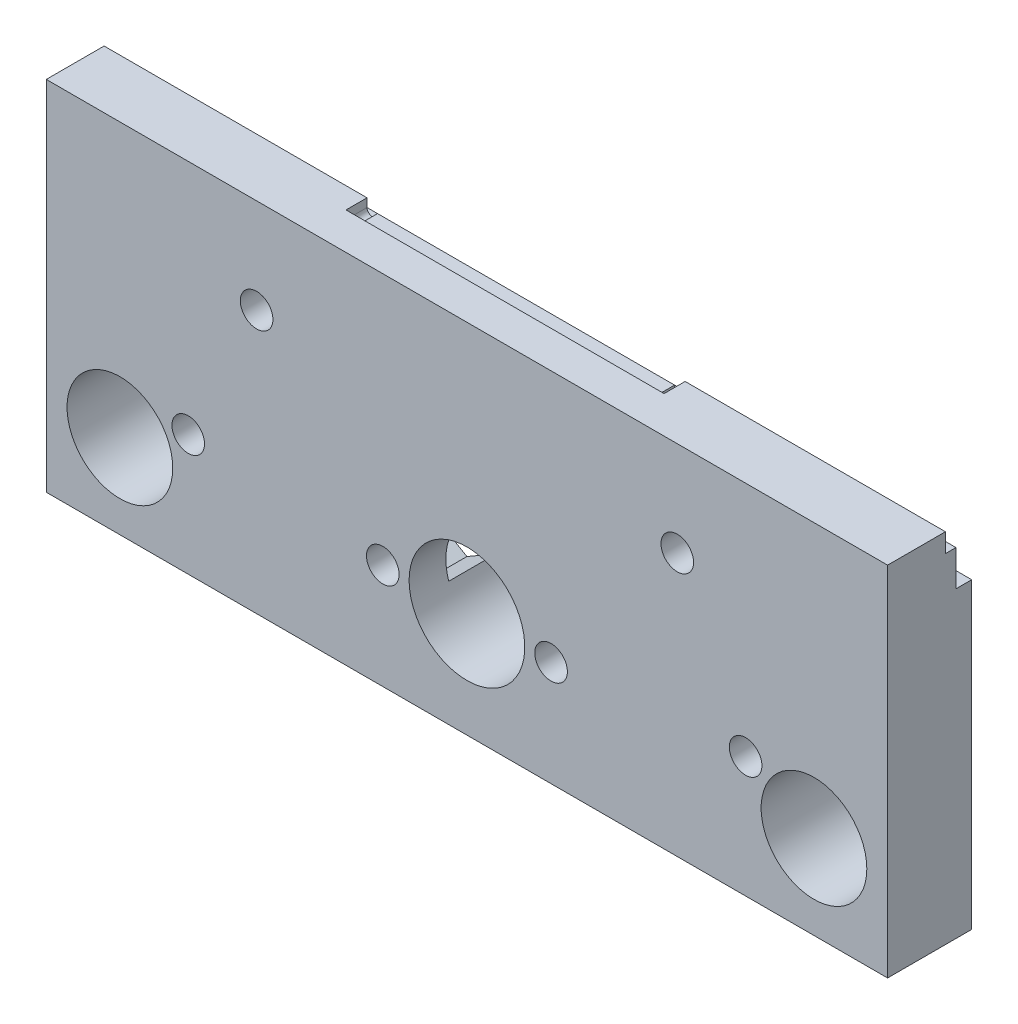
SolidWorks part; units mm, degrees
ref_plane "前视基准面" through (0, 0, 0) normal (0, 0, 1) x (1, 0, 0)
ref_plane "上视基准面" through (0, 0, 0) normal (0, 1, 0) x (1, 0, 0)
ref_plane "右视基准面" through (0, 0, 0) normal (1, 0, 0) x (0, 0, -1)
sketch "前视图草图" plane through (0, 0, 0) normal (0, 0, 1) x (1, 0, 0)
  line L0 (0, 0) -> (44.4821, 0) construction
  line L1 (0, 0) -> (0, 28.3185) construction
sketch "草图2" plane through (0, 0, 0) normal (0, 0, 1) x (1, 0, 0)
  line L0 (0, 0) -> (80, 0)
  line L1 (-200000, 0) -> (200044.4821, 0) construction
  line L2 (80, 0) -> (80, 34)
  line L3 (80, 34) -> (0, 34)
  line L4 (0, -200000) -> (0, 200028.3185) construction
  line L5 (0, 34) -> (0, 0)
  circle A0 centre (7, 8) radius 5.025
  circle A1 centre (40, 10) radius 4.05
  circle A2 centre (73, 8) radius 5.025
  dimension "D3" = 8
  dimension "D5" = 10
  dimension "D9" = 10.05
  dimension "D10" = 10.05
  dimension "D11" = 8.1
  dimension "D1" = 34
  dimension "D2" = 80
  dimension "D4" = 7
  dimension "D6" = 7
  dimension "D7" = 8
  dimension "D8" = 40
extrude "凸台-拉伸1" add sketch "草图2" along normal blind 8
sketch "草图3" plane through (0, 0, 8) normal (0, 0, 1) x (1, 0, 0)
  line L0 (16.088, 8) -> (31.4805, 8) construction
  line L1 (7, 8) -> (7, 16.8386) construction
  line L2 (73, 8) -> (73, 16.5917) construction
  line L4 (-200000, 0) -> (200044.4821, 0) construction
  circle A2 centre (23, 8) radius 2.55
  circle A3 centre (57, 8) radius 2.55
  dimension "D4" = 5.1
  dimension "D5" = 5.1
  dimension "D1" = 8
  dimension "D2" = 16
  dimension "D3" = 16
extrude "切除-拉伸1" [suppressed] cut sketch "草图3" against normal through all
sketch "草图4" plane through (80, 0, 0) normal (1, 0, 0) x (0, 0, -1)
  line L1 (0, -200000) -> (0, 200028.3185) construction
  line L2 (-1.5, 32.2) -> (-2.5, 32.2)
  line L3 (-2.5, 32.2) -> (-2.5, 34)
  line L4 (-8, 34) -> (0, 34) construction
  line L5 (-2.5, 34) -> (0, 34)
  line L6 (-1.5, 32.2) -> (-1.5, 28.8)
  line L7 (-1.5, 28.8) -> (0, 28.8)
  line L8 (0, 28.8) -> (0, 34)
  dimension "D1" = 3.4
  dimension "D2" = 2.5
  dimension "D3" = 1.5
  dimension "D4" = 1.8
extrude "切除-拉伸2" cut sketch "草图4" against normal through all
sketch "草图5" plane through (0, 0, 8) normal (0, 0, 1) x (1, 0, 0)
  line L0 (40, 10) -> (56.5376, 10) construction
  circle A0 centre (40, 10) radius 8 construction
  circle A1 centre (48, 10) radius 1.55
  circle A2 centre (32, 10) radius 1.55
  dimension "D1" = 3.1
  dimension "D2" = 3.1
  dimension "D3" = 16
extrude "切除-拉伸3" cut sketch "草图5" against normal through all
sketch "草图7" [suppressed] plane through (0, 0, 0) normal (0, 0, -1) x (-1, 0, 0)
  line L0 (-40, 12) -> (-40, -8.3696) construction
  line L1 (-23, 10) -> (-23, -2.3368) construction
  line L2 (200000, 0) -> (-200044.4821, 0) construction
  line L6 (-27.05, 10) -> (-27.05, 2.5)
  line L7 (-29.55, 0) -> (-16.45, 0)
  line L8 (-18.95, 2.5) -> (-18.95, 10)
  line L9 (-23, 8) -> (-23, 15.9045) construction
  line L13 (0, -200000) -> (0, 200028.3185) construction
  line L14 (-57, 8) -> (-57, 15.9045) construction
  line L15 (-57, 10) -> (-57, -2.3368) construction
  line L16 (-61.05, 2.5) -> (-61.05, 10)
  line L17 (-50.45, 0) -> (-63.55, 0)
  line L18 (-52.95, 10) -> (-52.95, 2.5)
  arc A1 (-18.95, 10) -> (-27.05, 10) centre (-23, 10) ccw
  arc A4 (-29.55, 0) -> (-27.05, 2.5) centre (-29.55, 2.5) ccw
  arc A5 (-18.95, 2.5) -> (-16.45, 0) centre (-16.45, 2.5) ccw
  arc A7 (-61.05, 2.5) -> (-63.55, 0) centre (-63.55, 2.5) cw
  arc A8 (-50.45, 0) -> (-52.95, 2.5) centre (-50.45, 2.5) cw
  arc A9 (-61.05, 10) -> (-52.95, 10) centre (-57, 10) cw
  dimension "D1" = 40
  dimension "D4" = 8.1
  dimension "D7" = 2.5
  dimension "D8" = 2.5
  dimension "D3" = 10
extrude "切除-拉伸4" [suppressed] cut sketch "草图7" against normal blind 6
sketch "草图8" plane through (0, 0, 0) normal (0, 0, -1) x (-1, 0, 0)
  line L0 (-40, 10) -> (-57.3165, 10) construction
  line L1 (-40, 20) -> (-40, 35.6562) construction
  line L2 (-30.5, 12.85) -> (-49.5, 12.85)
  line L3 (-49.5, 7.15) -> (-30.5, 7.15)
  line L4 (200000, 0) -> (-200044.4821, 0) construction
  line L5 (-80, 0) -> (-80, 28.8) construction
  line L6 (-45.15, 8.3546) -> (-45.15, 11.6454)
  line L7 (-45.15, 11.6454) -> (-48, 13.2909)
  line L8 (-48, 13.2909) -> (-50.85, 11.6454)
  line L9 (-50.85, 11.6454) -> (-50.85, 8.3546)
  line L10 (-50.85, 8.3546) -> (-48, 6.7091)
  line L11 (-48, 6.7091) -> (-45.15, 8.3546)
  line L12 (-34.85, 8.3546) -> (-32, 6.7091)
  line L13 (-32, 6.7091) -> (-29.15, 8.3546)
  line L14 (-29.15, 8.3546) -> (-29.15, 11.6454)
  line L15 (-29.15, 11.6454) -> (-32, 13.2909)
  line L16 (-32, 13.2909) -> (-34.85, 11.6454)
  line L17 (-34.85, 11.6454) -> (-34.85, 8.3546)
  arc A0 (-30.5, 7.15) -> (-30.5, 12.85) centre (-30.5, 10) ccw
  arc A1 (-49.5, 12.85) -> (-49.5, 7.15) centre (-49.5, 10) ccw
  circle A2 centre (-48, 10) radius 2.85 construction
  circle A3 centre (-32, 10) radius 2.85 construction
  dimension "D1" = 5.7
  dimension "D2" = 9.5
  dimension "D3" = 9.5
  dimension "D4" = 10
  dimension "D5" = 5.7
extrude "切除-拉伸5" cut sketch "草图8" against normal blind 4.5 contours L9 L10 L11 L6 L7 L8 | L17 L12 L13 L14 L15 L16
sketch "草图11" plane through (0, 0, 0) normal (0, 0, -1) x (-1, 0, 0)
  line L0 (0, 34) -> (-80, 34) construction
  line L1 (-80, 0) -> (-80, 28.8) construction
  line L2 (0, -200000) -> (0, 200028.3185) construction
  line L3 (-40, 20) -> (-40, 13.5744) construction
  line L4 (-28.772, 25) -> (-45.9396, 25) construction
  circle A0 centre (-60, 25) radius 1.55
  circle A1 centre (-20, 25) radius 1.55
  point P23 (-40, 20)
  dimension "D1" = 3.1
  dimension "D2" = 3.1
  dimension "D3" = 20
  dimension "D4" = 20
  dimension "D5" = 9
sketch "草图20" plane through (0, 0, 0) normal (0, 0, -1) x (-1, 0, 0)
  circle A0 centre (-40, 10) radius 5.5
  dimension "D1" = 11
extrude "切除-拉伸7" cut sketch "草图11" against normal through all contours A0 | A1 region at (60, 25, 0) region at (20, 25, 0)
sketch "草图12" plane through (0, 0, 0) normal (0, 0, -1) x (-1, 0, 0)
  line L0 (-62.5, 22.15) -> (-57.5, 22.15)
  line L1 (-57.5, 27.85) -> (-62.5, 27.85)
  line L4 (-80, 0) -> (-80, 28.8) construction
  line L5 (-39.1423, 25) -> (-43.2672, 25) construction
  line L6 (-60, 21) -> (-60, 25.2385) construction
  line L7 (-20, 21) -> (-20, 26.1603) construction
  line L8 (-40, 20) -> (-40, 24.3689) construction
  line L9 (-17.5, 27.85) -> (-22.5, 27.85)
  line L10 (-22.5, 22.15) -> (-17.5, 22.15)
  line L11 (0, -200000) -> (0, 200028.3185) construction
  line L12 (0, 34) -> (-80, 34) construction
  arc A0 (-62.5, 27.85) -> (-62.5, 22.15) centre (-62.5, 25) ccw
  arc A1 (-57.5, 22.15) -> (-57.5, 27.85) centre (-57.5, 25) ccw
  arc A4 (-17.5, 22.15) -> (-17.5, 27.85) centre (-17.5, 25) ccw
  arc A5 (-22.5, 27.85) -> (-22.5, 22.15) centre (-22.5, 25) ccw
  point P16 (-38, 21)
  point P28 (-40, 25)
  dimension "D2" = 20
  dimension "D3" = 5
  dimension "D4" = 2.5
  dimension "D5" = 20
  dimension "D6" = 9
  dimension "D1" = 2
sketch "草图19" plane through (0, 0, 2.5) normal (0, 0, -1) x (-1, 0, 0)
  line L0 (0, 34) -> (-80, 34) construction
  line L1 (-25, 34) -> (-55.2479, 34)
  line L2 (-25, 34) -> (-25, 33.2)
  line L3 (-26, 33.2) -> (-54.2479, 33.2)
  line L4 (-55.2479, 34) -> (-55.2479, 33.2)
  line L5 (0, -200000) -> (0, 200028.3185) construction
  line L7 (0, 32.2) -> (-80, 32.2) construction
  line L8 (-56.3335, 32.7) -> (-52.9089, 32.7) construction
  line L9 (-55.2479, 1028.5823) -> (-55.2479, 33.2) construction
  line L10 (-25, 1028.5823) -> (-25, 32.7) construction
  line L11 (-55.2479, 32.7) -> (-55.2479, -973.3) construction
  line L12 (-25, 32.7) -> (-25, -973.3) construction
  arc A3 (-55.2479, 33.2) -> (-54.2479, 33.2) centre (-54.7479, 33.2) ccw
  arc A6 (-26, 33.2) -> (-25, 33.2) centre (-25.5, 33.2) ccw
  dimension "D3" = 1
  dimension "D4" = 1
  dimension "D2" = 0.8
  dimension "D1" = 0.5
  dimension "D9" = 25
extrude "切除-拉伸11" cut sketch "草图19" against normal blind 2
sketch "草图22" plane through (0, 0, 0) normal (0, 0, -1) x (-1, 0, 0)
  line L0 (-66.5, 0) -> (-66.5, 28.8) construction
  line L1 (200000, 0) -> (-200044.4821, 0) construction
  line L2 (0, 28.8) -> (-80, 28.8) construction
  line L3 (-80, 11.5) -> (0, 11.5) construction
  line L4 (-80, 0) -> (-80, 28.8) construction
  line L5 (0, -200000) -> (0, 200028.3185) construction
  line L7 (-40, 32.2) -> (-40, 0) construction
  line L8 (0, 32.2) -> (-80, 32.2) construction
  line L10 (-40, -199980) -> (-40, 200024.3689) construction
  circle A0 centre (-66.5, 11.5) radius 1.55
  circle A1 centre (-13.5, 11.5) radius 1.55
  dimension "D3" = 3.1
  dimension "D1" = 11.5
  dimension "D2" = 13.5
extrude "切除-拉伸13" cut sketch "草图22" against normal through all
extrude "切除-拉伸14" cut sketch "草图20" against normal through all contours A0
